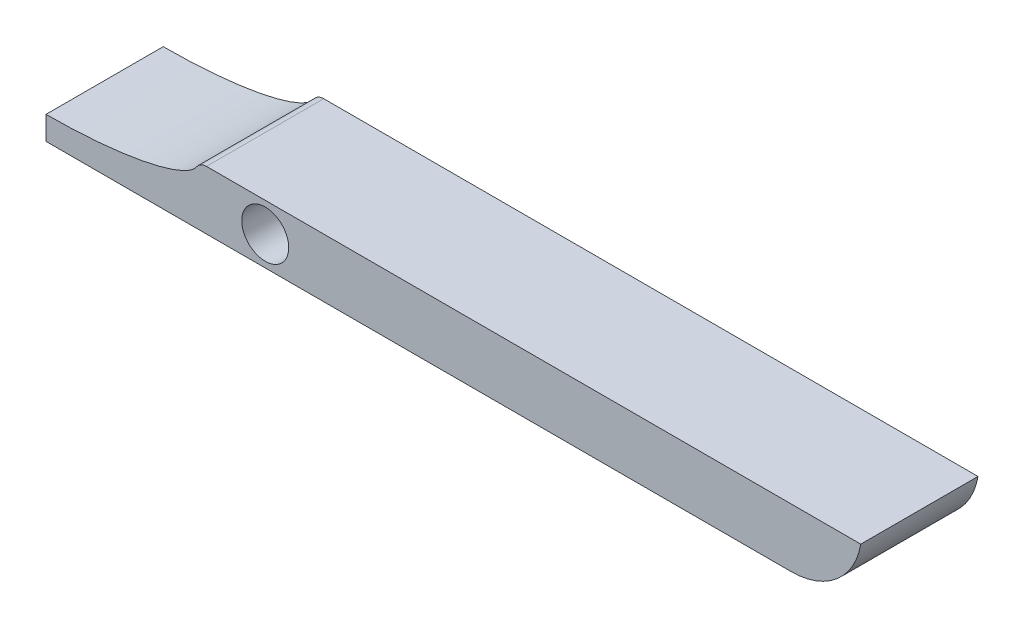
SolidWorks part; units mm, degrees
ref_plane "Front Plane" through (0, 0, 0) normal (0, 0, 1) x (1, 0, 0)
ref_plane "Top Plane" through (0, 0, 0) normal (0, 1, 0) x (1, 0, 0)
ref_plane "Right Plane" through (0, 0, 0) normal (1, 0, 0) x (0, 0, -1)
sketch "Sketch1" plane through (0, 0, 0) normal (0, 1, 0) x (1, 0, 0)
  line L1 (17.375, -2.5) -> (-17.375, -2.5)
  line L2 (17.375, -2.5) -> (17.375, 2.5)
  line L3 (17.375, 2.5) -> (-17.375, 2.5)
  line L4 (-17.375, -2.5) -> (-17.375, 2.5)
  line L5 (17.375, -2.5) -> (-17.375, 2.5) construction
  line L6 (17.375, 2.5) -> (-17.375, -2.5) construction
  point P0 (0, 0)
  dimension "D1" = 34.75
  dimension "D2" = 5
extrude "Boss-Extrude1" add sketch "Sketch1" along normal blind 2.5
hole_wizard "Ø1.0mm Dowel Hole1" positions "Sketch2" profile "Sketch3" hole size "Ø1.0" standard "ANSI Metric" end condition through all
sketch "Sketch2" plane through (0, 0, 2.5) normal (0, 0, 1) x (1, 0, 0)
  line L0 (-17.375, 2.5) -> (17.375, 2.5) construction
  line L1 (17.375, 2.5) -> (17.375, 0) construction
  point P0 (-8.025, 1.25)
  dimension "D1" = 1.25
  dimension "D2" = 25.4
sketch "Sketch3" plane through (-8.025, 1.25, 2.5) normal (1, 0, 0) x (0, -1, 0)
  line L0 (0, 0) -> (0, 5)
  line L1 (0, 5) -> (1.0025, 5)
  line L2 (1.0025, 5) -> (1.0025, 0)
  line L5 (1.0025, 0) -> (0, 0)
  line L11 (0, -6.35) -> (0, 107.95) construction
  dimension "Thru Hole Dia." = 2.005
  dimension "Thru Hole Depth" = 5
sketch "Sketch15" plane through (0, 0, 2.5) normal (0, 0, 1) x (1, 0, 0)
  line L0 (-17.375, 2.5) -> (17.375, 2.5) construction
  line L1 (-17.375, 0) -> (17.375, 0) construction
  ellipse E0 centre (-17.375, 2.5) end of major axis (-10.875, 2.5) minor radius 1.5
  dimension "D1" = 6.5
  dimension "D2" = 1
extrude "Cut-Extrude1" cut sketch "Sketch15" against normal blind 10
fillet "Fillet1" radius 0.5 1 edges at (-10.875, 2.5, 0)
fillet "Fillet2" radius 3 1 edges at (17.375, 0, 0)
